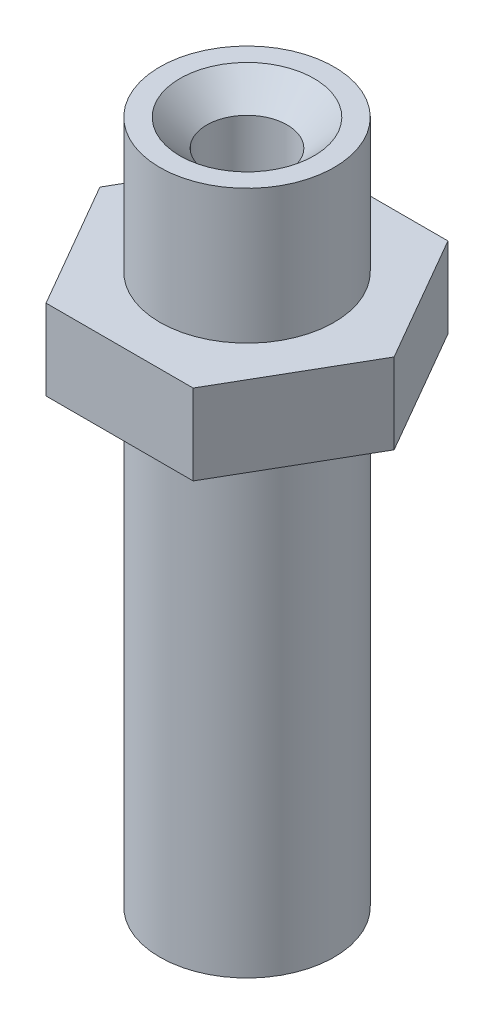
SolidWorks part; units mm, degrees
ref_plane "Front Plane" through (0, 0, 0) normal (0, 0, 1) x (1, 0, 0)
ref_plane "Top Plane" through (0, 0, 0) normal (0, 1, 0) x (1, 0, 0)
ref_plane "Right Plane" through (0, 0, 0) normal (1, 0, 0) x (0, 0, -1)
sketch "Szkic1" plane through (0, 0, 0) normal (0, 1, 0) x (1, 0, 0)
  line L1 (-10.9697, 0) -> (-5.4848, -9.5)
  line L2 (-5.4848, -9.5) -> (5.4848, -9.5)
  line L3 (5.4848, -9.5) -> (10.9697, 0)
  line L4 (10.9697, 0) -> (5.4848, 9.5)
  line L5 (5.4848, 9.5) -> (-5.4848, 9.5)
  line L6 (-5.4848, 9.5) -> (-10.9697, 0)
  circle A0 centre (0, 0) radius 9.5 construction
  circle A1 centre (0, 0) radius 6.5
  circle A2 centre (0, 0) radius 3
  dimension "D2" = 13
  dimension "D3" = 6
  dimension "D1" = 19
extrude "Dodanie-wyciągnięcie1" add sketch "Szkic1" along normal blind 6 contours L5 L6 L1 L2 L3 L4 A1 region at (-7.9759, 0, -4.6049)
extrude "Dodanie-wyciągnięcie2" add sketch "Szkic1<3>" along normal blind 16 contours A1 A2 region at (-6.3162, 0, 0)
sketch "Szkic1<3>" plane through (0, 0, 0) normal (0, 1, 0) x (1, 0, 0) same geometry as "Szkic1"
extrude "Dodanie-wyciągnięcie3" add sketch "Szkic1<4>" along normal blind 16 and the other way blind 35 contours A1 A2 region at (-6.3162, 0, 0)
sketch "Szkic1<4>" plane through (0, 0, 0) normal (0, 1, 0) x (1, 0, 0) same geometry as "Szkic1"
chamfer "Sfazowanie1" distance 2 angle 45 1 edges at (0, 16, 3)
chamfer "Sfazowanie2" distance 2 angle 45 1 edges at (0, -35, 3)
